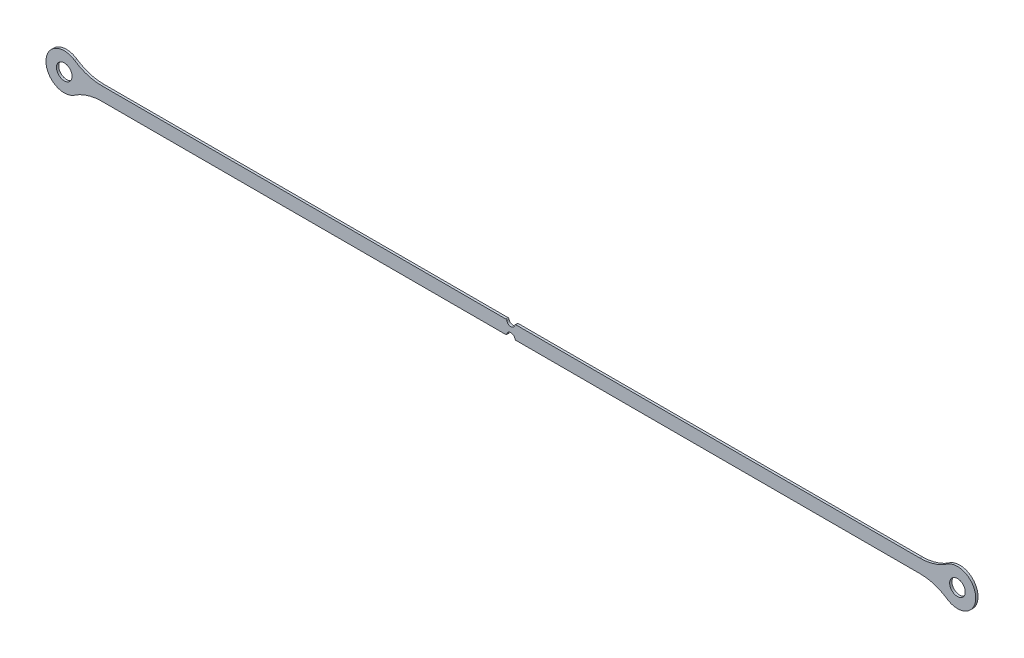
SolidWorks part; units mm, degrees
ref_plane "Front Plane" through (0, 0, 0) normal (0, 0, 1) x (1, 0, 0)
ref_plane "Top Plane" through (0, 0, 0) normal (0, 1, 0) x (1, 0, 0)
ref_plane "Right Plane" through (0, 0, 0) normal (1, 0, 0) x (0, 0, -1)
sketch "Sketch1" plane through (0, 0, 0) normal (0, 0, 1) x (1, 0, 0)
  line L0 (0, -0.5623) -> (0, -10.0623) construction
  line L7 (0, 1.35) -> (0, -1.35)
  line L10 (232, 0) -> (-232, 0) construction
  line L11 (2.6024, 3.5) -> (212.5578, 3.5)
  line L12 (2.6024, -3.5) -> (212.5578, -3.5)
  line L13 (-2.6024, -3.5) -> (-212.5578, -3.5)
  line L14 (-2.6024, 3.5) -> (-212.5578, 3.5)
  arc A0 (226.6463, -7.8478) -> (226.6463, 7.8478) centre (232, 0) ccw
  circle A1 centre (232, 0) radius 4.05
  arc A6 (-2.1114, 3.0943) -> (2.1114, 3.0943) centre (0, 3.5) ccw
  arc A7 (-2.1114, -3.0943) -> (2.1114, -3.0943) centre (0, -3.5) cw
  arc A8 (226.6463, 7.8478) -> (212.5578, 3.5) centre (212.5578, 28.5) cw
  arc A9 (226.6463, -7.8478) -> (212.5578, -3.5) centre (212.5578, -28.5) ccw
  arc A10 (2.6024, 3.5) -> (2.1114, 3.0943) centre (2.6024, 3) ccw
  arc A11 (2.6024, -3.5) -> (2.1114, -3.0943) centre (2.6024, -3) cw
  arc A12 (-2.6024, -3.5) -> (-2.1114, -3.0943) centre (-2.6024, -3) ccw
  arc A13 (-2.6024, 3.5) -> (-2.1114, 3.0943) centre (-2.6024, 3) cw
  arc A14 (-226.6463, -7.8478) -> (-212.5578, -3.5) centre (-212.5578, -28.5) cw
  arc A15 (-226.6463, 7.8478) -> (-212.5578, 3.5) centre (-212.5578, 28.5) ccw
  circle A16 centre (-232, 0) radius 4.05
  arc A17 (-226.6463, -7.8478) -> (-226.6463, 7.8478) centre (-232, 0) cw
  point P0 (0, 0)
  point P19 (223.1682, 3.5)
  point P22 (223.1682, -3.5)
  point P25 (2.15, 3.5)
  point P28 (2.15, -3.5)
  point P30 (0, 0)
  point P43 (-2.15, -3.5)
  point P44 (-2.15, 3.5)
  point P45 (-223.1682, -3.5)
  point P46 (-223.1682, 3.5)
  dimension "D2" = 9.5
  dimension "D4" = 8.1
  dimension "D5" = 3.5
  dimension "D6" = 7
  dimension "D7" = 25
  dimension "D8" = 25
  dimension "D9" = 0.5
  dimension "D10" = 0.5
  dimension "D1" = 232
extrude "Boss-Extrude1" add sketch "Sketch1" along normal blind 1.2 contours L0 L7 | L0 L7 A0 A1 region at (128.6005, 0, 0) region at (-128.6005, 0, 0)
